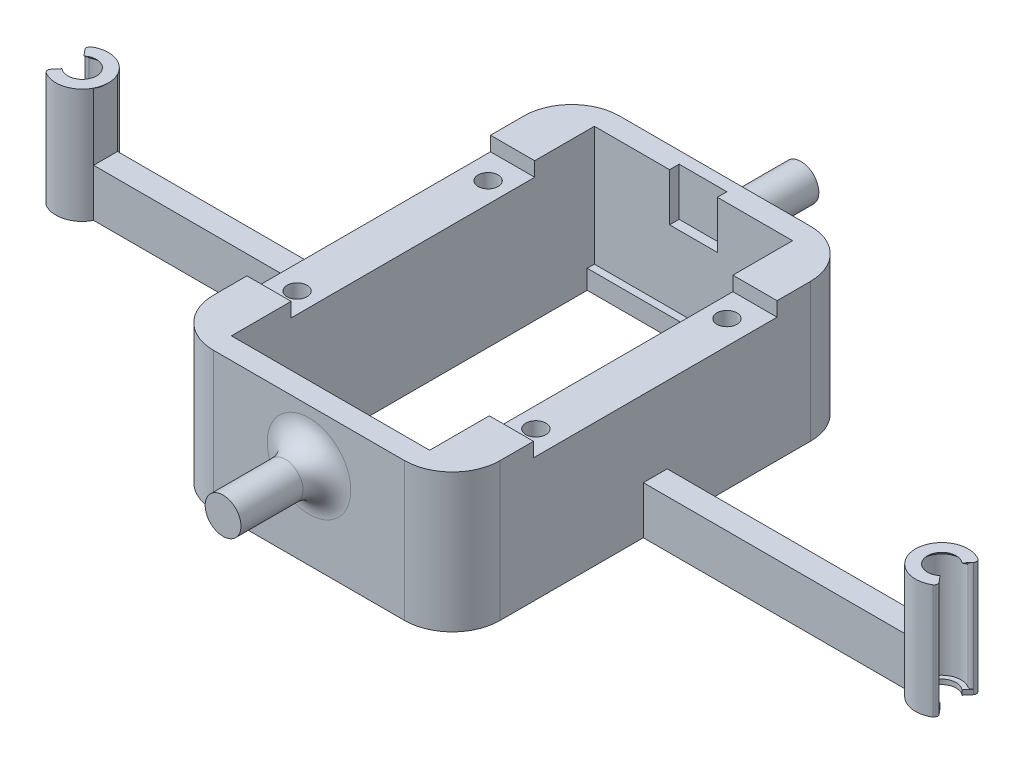
SolidWorks part; units mm, degrees
ref_plane "Front" through (0, 0, 0) normal (0, 0, 1) x (1, 0, 0)
ref_plane "Top" through (0, 0, 0) normal (0, 1, 0) x (1, 0, 0)
ref_plane "Right" through (0, 0, 0) normal (1, 0, 0) x (0, 0, -1)
sketch "Sketch4" plane through (0, 0, 0) normal (0, 1, 0) x (1, 0, 0)
  line L0 (0, 0) -> (-64736.8485, 0) construction
  line L1 (0, 0) -> (0, 64736.8485) construction
  line L4 (-30, 2.5) -> (-30, 42.5)
  line L5 (-30, 42.5) -> (30, 42.5)
  line L12 (-30, 2.5) -> (-85.101, 2.5)
  line L13 (-90, 0) -> (-93.5353, 4.2132) construction
  line L14 (-93.5353, 4.2132) -> (-92.5712, 3.0642)
  line L15 (93.5353, 4.2132) -> (92.5712, 3.0642)
  line L16 (30, 2.5) -> (85.101, 2.5)
  line L17 (30, 2.5) -> (30, 42.5)
  line L18 (30, -2.5) -> (30, -42.5)
  line L19 (30, -2.5) -> (85.101, -2.5)
  line L20 (93.5353, -4.2132) -> (92.5712, -3.0642)
  line L21 (-93.5353, -4.2132) -> (-92.5712, -3.0642)
  line L22 (-30, -2.5) -> (-85.101, -2.5)
  line L23 (-30, -42.5) -> (30, -42.5)
  line L24 (-30, -2.5) -> (-30, -42.5)
  arc A1 (-92.5712, -3.0642) -> (-92.5712, 3.0642) centre (-90, 0) ccw
  arc A8 (-85.101, 2.5) -> (-93.5353, 4.2132) centre (-90, 0) ccw
  arc A9 (85.101, 2.5) -> (93.5353, 4.2132) centre (90, 0) cw
  arc A10 (92.5712, -3.0642) -> (92.5712, 3.0642) centre (90, 0) cw
  arc A11 (85.101, -2.5) -> (93.5353, -4.2132) centre (90, 0) ccw
  arc A12 (-85.101, -2.5) -> (-93.5353, -4.2132) centre (-90, 0) cw
  point P13 (0, -42.5)
  point P14 (-90, 0)
  point P19 (90, 0)
  point P33 (0, 42.5)
  dimension "D4" = 8
  dimension "D3" = 11
  dimension "D1" = 85
  dimension "D2" = 60
  dimension "D5" = 5
  dimension "D6" = 90
  dimension "D7" = 50
extrude "Boss-Extrude1" add sketch "Sketch4" along normal blind 24
sketch "Sketch22" plane through (0, 24, 0) normal (0, 1, 0) x (1, 0, 0)
  line L1 (-30, -42.5) -> (30, -42.5)
  line L2 (-30, -42.5) -> (-30, 42.5)
  line L3 (-30, 42.5) -> (30, 42.5)
  line L4 (30, -42.5) -> (30, 42.5)
  line L5 (-30, -42.5) -> (30, 42.5) construction
  line L6 (-30, 42.5) -> (30, -42.5) construction
  point P0 (0, 0)
extrude "Boss-Extrude6" add sketch "Sketch22" along normal blind 5
sketch "Sketch5" plane through (0, 29, 0) normal (0, 1, 0) x (1, 0, 0)
  line L1 (-20.75, -38) -> (20.75, -38)
  line L2 (-20.75, -38) -> (-20.75, 38)
  line L3 (-20.75, 38) -> (20.75, 38)
  line L4 (20.75, -38) -> (20.75, 38)
  line L5 (-20.75, -38) -> (20.75, 38) construction
  line L6 (-20.75, 38) -> (20.75, -38) construction
  point P0 (0, 0)
  dimension "D1" = 41.5
  dimension "D2" = 76
extrude "Cut-Extrude1" cut sketch "Sketch5" against normal blind 25
sketch "Sketch17" plane through (0, 29, 0) normal (0, 1, 0) x (1, 0, 0)
  line L1 (-30, -25.5) -> (30, -25.5)
  line L2 (-30, -25.5) -> (-30, 25.5)
  line L3 (-30, 25.5) -> (30, 25.5)
  line L4 (30, -25.5) -> (30, 25.5)
  line L5 (-30, -25.5) -> (30, 25.5) construction
  line L6 (-30, 25.5) -> (30, -25.5) construction
  point P0 (0, 0)
  dimension "D1" = 60
  dimension "D2" = 51
extrude "Cut-Extrude10" cut sketch "Sketch17" against normal blind 3
sketch "Sketch8" plane through (0, 0, 2.5) normal (0, 0, 1) x (1, 0, 0)
  line L0 (-30, 24) -> (-30, 0) construction
  line L1 (-85.101, 24) -> (-30, 24)
  line L2 (-85.101, 24) -> (-85.101, 10)
  line L3 (-85.101, 10) -> (-30, 10)
  line L4 (-30, 24) -> (-30, 10)
  line L5 (85.101, 24) -> (85.101, 0) construction
  line L6 (30, 24) -> (85.101, 24)
  line L7 (30, 24) -> (30, 10)
  line L8 (30, 10) -> (85.101, 10)
  line L9 (85.101, 24) -> (85.101, 10)
  line L10 (-85.101, 0) -> (-30, 0) construction
  line L11 (30, 0) -> (85.101, 0) construction
  line L12 (30, 24) -> (85.101, 24) construction
  line L13 (30, 29) -> (30, 0) construction
  dimension "D1" = 10
  dimension "D2" = 10
extrude "Cut-Extrude3" cut sketch "Sketch8" against normal through all
fillet "Fillet4" radius 10 4 edges at (-30, 14.5, -42.5) (30, 14.5, -42.5) (30, 14.5, 42.5) (-30, 14.5, 42.5)
sketch "Sketch11" plane through (0, 24, 0) normal (0, 1, 0) x (1, 0, 0)
  line L0 (-90, 0) -> (-93.5353, 4.2132) construction
  line L1 (-90, 0) -> (-93.5353, -4.2132) construction
  line L2 (-93.5353, 4.2132) -> (-91.9284, 2.2981)
  line L3 (-93.5353, -4.2132) -> (-91.9284, -2.2981)
  arc A0 (-93.5353, -4.2132) -> (-93.5353, 4.2132) centre (-90, 0) ccw
  arc A1 (-91.9284, -2.2981) -> (-91.9284, 2.2981) centre (-90, 0) ccw
  circle A2 centre (-90, 0) radius 5.5 construction
  circle A3 centre (-90, 0) radius 3 construction
  dimension "D2" = 11
  dimension "D3" = 100
  dimension "D1" = 2.5
extrude "Boss-Extrude3" add sketch "Sketch11" against normal blind 1 draft 45
mirror "Mirror6" about plane through (0, 0, 0) normal (1, 0, 0) of "Boss-Extrude3"
sketch "Sketch12" plane through (0, 0, 0) normal (0, -1, 0) x (1, 0, 0)
  line L0 (-90, 0) -> (-93.5353, 4.2132) construction
  line L1 (-90, 0) -> (-93.5353, -4.2132) construction
  line L2 (-93.5353, 4.2132) -> (-91.9284, 2.2981)
  line L3 (-91.9284, -2.2981) -> (-93.5353, -4.2132)
  arc A0 (-93.5353, -4.2132) -> (-93.5353, 4.2132) centre (-90, 0) ccw
  arc A1 (-91.9284, -2.2981) -> (-91.9284, 2.2981) centre (-90, 0) ccw
  dimension "D1" = 2.5
extrude "Boss-Extrude4" add sketch "Sketch12" against normal blind 1
mirror "Mirror5" about plane through (0, 0, 0) normal (1, 0, 0) of "Boss-Extrude4"
fillet "Fillet3" radius 0.75 8 edges at (93.5353, 12, 4.2132) (92.5712, 12.5, 3.0642) (92.5712, 12.5, -3.0642) (93.5353, 12, -4.2132) (-93.5353, 12, 4.2132) (-92.5712, 12.5, 3.0642) (-93.5353, 12, -4.2132) (-92.5712, 12.5, -3.0642)
sketch "Sketch15" plane through (0, 26, 0) normal (0, 1, 0) x (1, 0, 0)
  line L0 (0, 0) -> (0, 50000) construction
  line L1 (-20.75, 25.5) -> (-30, 25.5) construction
  line L2 (0, 0) -> (50000, 0) construction
  circle A0 centre (-25, 20) radius 2.1
  circle A1 centre (25, 20) radius 2.1
  circle A2 centre (25, -20) radius 2.1
  circle A3 centre (-25, -20) radius 2.1
  dimension "D1" = 4.2
  dimension "D2" = 50
  dimension "D3" = 5.5
  dimension "D4" = 40
extrude "Cut-Extrude8" cut sketch "Sketch15" against normal through all
sketch "Sketch20" plane through (0, 4, 0) normal (0, 1, 0) x (1, 0, 0)
  line L0 (20.75, 25.5) -> (20.75, 38) construction
  line L1 (-20.75, -36.5) -> (20.75, -36.5)
  line L2 (-20.75, -36.5) -> (-20.75, 36.5)
  line L3 (-20.75, 36.5) -> (20.75, 36.5)
  line L4 (20.75, -36.5) -> (20.75, 36.5)
  line L5 (-20.75, -36.5) -> (20.75, 36.5) construction
  line L6 (-20.75, 36.5) -> (20.75, -36.5) construction
  line L7 (20.75, 38) -> (-20.75, 38) construction
  point P0 (0, 0)
  dimension "D1" = 1.5
extrude "Cut-Extrude11" cut sketch "Sketch20" against normal blind 5
sketch "Sketch21" plane through (0, 0, 42.5) normal (0, 0, 1) x (1, 0, 0)
  circle A0 centre (0, 18) radius 3.75
  dimension "D1" = 7.5
  dimension "D2" = 18
extrude "Boss-Extrude5" add sketch "Sketch21" along normal blind 18
mirror "Mirror9" about plane through (0, 0, 0) normal (0, 0, 1) of "Boss-Extrude5"
fillet "Fillet5" radius 5 2 edges at (-3.75, 18, 42.5) (3.75, 18, -42.5)
sketch "Sketch24" plane through (0, 29, 0) normal (0, 1, 0) x (1, 0, 0)
  line L0 (-5, 40) -> (-5, 38)
  line L1 (-5, 40) -> (5, 40)
  line L2 (-5, 38) -> (5, 38)
  line L3 (5, 40) -> (5, 38)
  line L4 (-5, 40) -> (5, 38) construction
  line L5 (-5, 38) -> (5, 40) construction
  line L6 (20.75, 38) -> (-20.75, 38) construction
  point P0 (0, 38)
  point P1 (0, 39)
  dimension "D1" = 2
  dimension "D2" = 10
extrude "Cut-Extrude12" cut sketch "Sketch24" against normal blind 10
